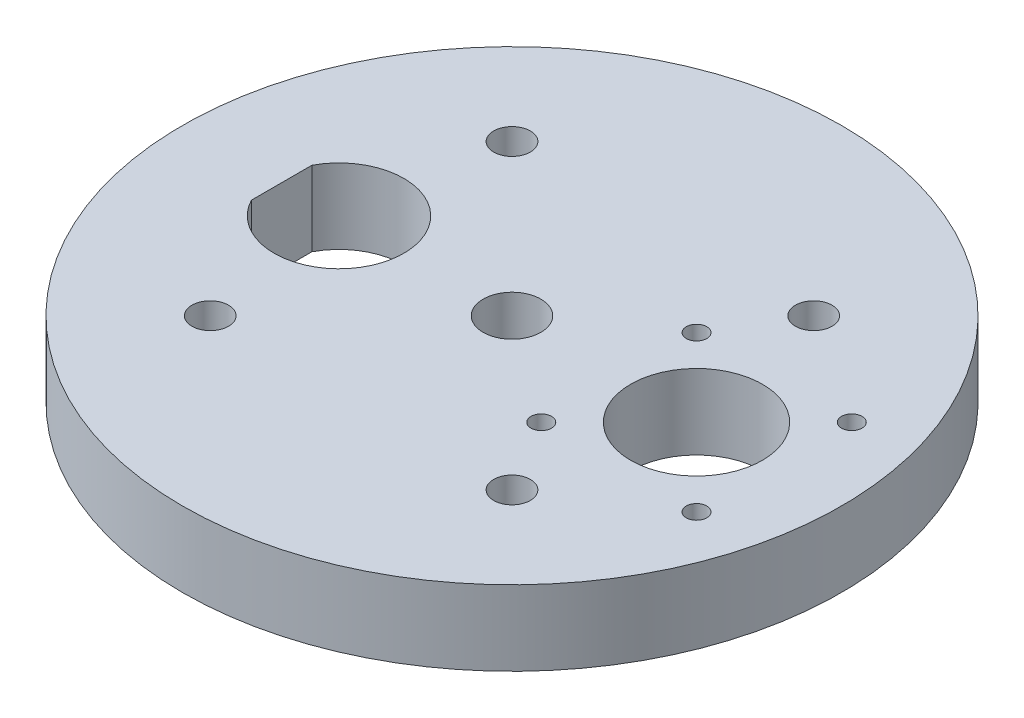
SolidWorks part; units mm, degrees
ref_plane "Front Plane" through (0, 0, 0) normal (0, 0, 1) x (1, 0, 0)
ref_plane "Top Plane" through (0, 0, 0) normal (0, 1, 0) x (1, 0, 0)
ref_plane "Right Plane" through (0, 0, 0) normal (1, 0, 0) x (0, 0, -1)
sketch "Sketch2" plane through (0, 0, 0) normal (0, 1, 0) x (1, 0, 0)
  circle A0 centre (0, 0) radius 57.15
  dimension "D1" = 114.3
extrude "Boss-Extrude1" add sketch "Sketch2" along normal blind 13 contours A0
sketch "Sketch6" plane through (0, 13, 0) normal (0, 1, 0) x (1, 0, 0)
  circle A0 centre (-26.1629, -26.1629) radius 3.175
  circle A1 centre (26.1629, -26.1629) radius 3.175
  circle A2 centre (-26.1629, 26.1631) radius 3.175
  circle A3 centre (26.1629, 26.1631) radius 3.175
  dimension "D1" = 6.35
  dimension "D2" = 74
  dimension "D3" = 26.1629
  dimension "D4" = 26.1629
  dimension "D5" = 26.1629
extrude "Cut-Extrude1" cut sketch "Sketch6" against normal up to next
sketch "Sketch7" plane through (0, 13, 0) normal (0, 1, 0) x (1, 0, 0)
  circle A0 centre (32, 0) radius 11.43
  circle A3 centre (18.54, -13.464) radius 1.778
  circle A4 centre (18.54, 13.46) radius 1.778
  circle A5 centre (45.46, 13.46) radius 1.778
  circle A6 centre (45.46, -13.464) radius 1.778
  circle A8 centre (26.1629, -26.1629) radius 3.175 construction
  dimension "D1" = 22.86
  dimension "D2" = 3.556
  dimension "D3" = 3.556
  dimension "D4" = 3.556
  dimension "D5" = 3.556
  dimension "D6" = 13.46
  dimension "D7" = 13.46
  dimension "D8" = 13.46
  dimension "D9" = 13.464
  dimension "D10" = 32
extrude "Cut-Extrude2" cut sketch "Sketch7" against normal through all
sketch "Sketch8" plane through (0, 13, 0) normal (0, 1, 0) x (1, 0, 0)
  line L0 (-39.95, 5.2498) -> (-39.95, -5.2498)
  circle A2 centre (0, 0) radius 5
  arc A3 (-39.95, -5.2498) -> (-39.95, 5.2498) centre (-30, 0) ccw
  dimension "D1" = 9.95
  dimension "D3" = 10
  dimension "D4" = 22.5
  dimension "D5" = 30
extrude "Cut-Extrude3" cut sketch "Sketch8" against normal through all
equation "\"width\"=26.1629"
equation "\"D4@Sketch6\"=\"width\""
equation "\"D3@Sketch6\"=\"width\""
equation "\"D5@Sketch6\"=\"width\""
